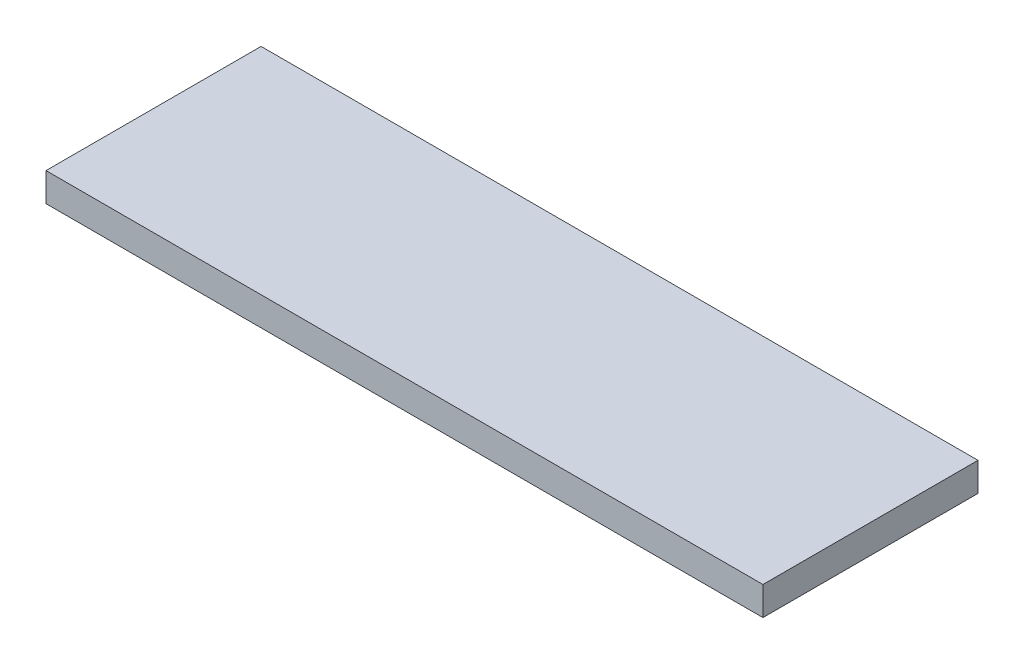
SolidWorks part; units mm, degrees
material "ABS PC"
ref_plane "Front Plane" through (0, 0, 0) normal (0, 0, 1) x (1, 0, 0)
ref_plane "Top Plane" through (0, 0, 0) normal (0, 1, 0) x (1, 0, 0)
ref_plane "Right Plane" through (0, 0, 0) normal (1, 0, 0) x (0, 0, -1)
sketch "Sketch1" plane through (0, 0, 0) normal (0, 1, 0) x (1, 0, 0)
  line L1 (0, 0) -> (150, 0)
  line L2 (0, 0) -> (0, 45)
  line L3 (0, 45) -> (150, 45)
  line L4 (150, 0) -> (150, 45)
  dimension "D1" = 45
  dimension "D2" = 150
extrude "Boss-Extrude1" add sketch "Sketch1" along normal blind 6
